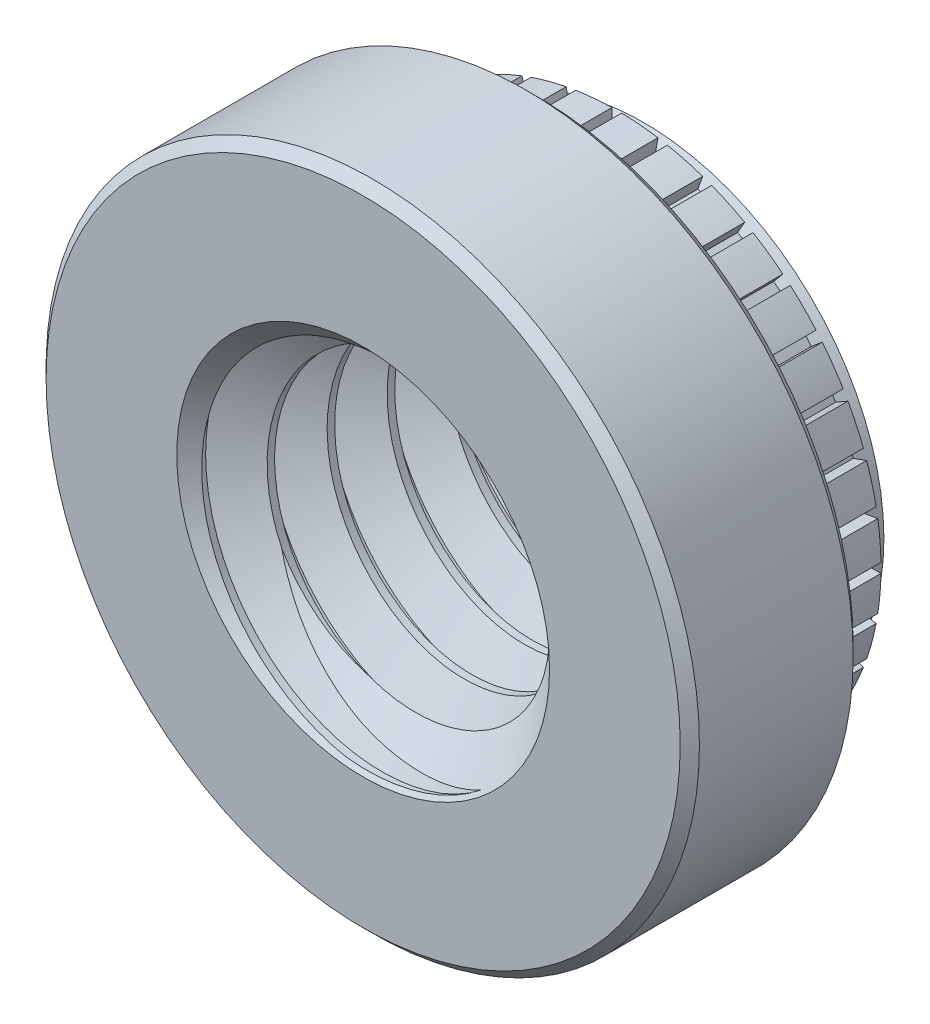
SolidWorks part; units mm, degrees
ref_plane "Front Plane" through (0, 0, 0) normal (0, 0, 1) x (1, 0, 0)
ref_plane "Top Plane" through (0, 0, 0) normal (0, 1, 0) x (1, 0, 0)
ref_plane "Right Plane" through (0, 0, 0) normal (1, 0, 0) x (0, 0, -1)
sketch "Sketch1" plane through (0, 0, 0) normal (0, 0, 1) x (1, 0, 0)
  circle A0 centre (0, 0) radius 4.318
  dimension "A" = 8.636
extrude "Extrude1" add sketch "Sketch1" against normal blind 2.286
sketch "Sketch15" plane through (0, 0, -2.286) normal (0, 0, -1) x (-1, 0, 0)
  circle A0 centre (0, 0) radius 3.175
  dimension "hole dia" = 6.35
sketch "Sketch2" plane through (0, 0, -2.286) normal (0, 0, -1) x (-1, 0, 0)
  circle A0 centre (0, 0) radius 3.4925
  dimension "D1" = 6.985
extrude "Extrude2" add sketch "Sketch2" along normal blind 1.4224
sketch "Sketch3" plane through (0, 0, -3.7084) normal (0, 0, -1) x (-1, 0, 0)
  line L0 (0, 3.302) -> (0, 4.318)
  circle A1 centre (0, 0) radius 4.318 construction
  circle A2 centre (0, 0) radius 3.302
  circle A3 centre (0, 0) radius 3.302 construction
  dimension "D1" = 0.1905
extrude "Cut-Extrude-Thin1" cut sketch "Sketch3" against normal up to surface (1.4224 mm away) thin up to face at (4.318, 0, -2.286) thin type mid plane wall 0.127
pattern_circular "CirPattern1" count 36 over 360 about axis through (0, 0, 0) along (0, 0, 1) of "Cut-Extrude-Thin1"
sketch "Sketch5" plane through (0, 0, -3.7084) normal (0, 0, -1) x (-1, 0, 0)
  circle A0 centre (0, 0) radius 4.318 construction
  circle A3 centre (0, 0) radius 3.175
  dimension "C" = 6.35
extrude "Cut-Extrude1" cut sketch "Sketch5" against normal blind 0.3556 draft 20 flip side to cut draft outward yes
chamfer "Chamfer2" distance 0.127 angle 45 2 edges at (4.318, 0, 0) (4.318, 0, -2.286)
sketch "Sketch7" plane through (0, 0, 0) normal (0, 0, 1) x (1, 0, 0)
  circle A0 centre (0, 0) radius 2.413
  dimension "Thread Od" = 4.826
extrude "Cut-Extrude3" cut sketch "Sketch7" against normal through all
sketch "Sketch8" plane through (0, 0, -3.7084) normal (0, 0, -1) x (-1, 0, 0)
  circle A0 centre (0, 0) radius 2.413 construction
  circle A1 centre (0, 0) radius 2.413
curve "Helix/Spiral1" pitch 0.7937 height 6.8834 turns 8.672 parameters "pitch"=0.7937
sketch "Sketch9" plane through (0, 0, 0) normal (1, 0, 0) x (0, 0, -1)
  line L0 (4.4029, 2.413) -> (4.1053, 1.8974)
  line L1 (4.1053, 1.8974) -> (4.0061, 1.8974)
  line L2 (4.0061, 1.8974) -> (3.7084, 2.413)
  line L3 (4.4029, 2.413) -> (3.7084, 2.413)
  line L4 (4.0557, 2.413) -> (4.0557, 1.8974) construction
  line L5 (4.2541, 2.1552) -> (3.8572, 2.1552) construction
  line L6 (3.7084, -2.413) -> (3.7084, 2.413) construction
  dimension "D1" = 60
  dimension "D2" = 0.0992
  dimension "D3" = 0.3969
sweep "Sweep1" add profiles "Sketch9" path "Helix/Spiral1"
sketch "Sketch10" plane through (0, 0, 0) normal (0, 0, 1) x (1, 0, 0)
  circle A0 centre (0, 0) radius 4.318 construction
  circle A1 centre (0, 0) radius 4.318
extrude "Cut-Extrude4" cut sketch "Sketch10" along normal through all
sketch "Sketch11" plane through (0, 0, -3.7084) normal (0, 0, -1) x (-1, 0, 0)
  circle A1 centre (0, 0) radius 3.175 construction
  circle A2 centre (0, 0) radius 3.175
extrude "Cut-Extrude5" cut sketch "Sketch11" along normal through all
sketch "Sketch13" plane through (0, 0, 0) normal (0, 0, 1) x (1, 0, 0)
  circle A2 centre (0, 0) radius 2.4638
  circle A3 centre (0, 0) radius 2.4638
  dimension "D1" = 0.0508
extrude "Cut-Extrude6" cut sketch "Sketch13" against normal through all draft 45
sketch "Sketch14" plane through (0, 0, -3.7084) normal (0, 0, -1) x (-1, 0, 0)
  circle A2 centre (0, 0) radius 2.4638
  circle A3 centre (0, 0) radius 2.4638
  dimension "D1" = 0.0508
extrude "Cut-Extrude7" cut sketch "Sketch14" against normal through all draft 45
equation "\"D3@Helix/Spiral1\" = \"B@Extrude1\"+\"panel min.@Extrude2\"+.125"
equation "\"D2@Sketch9\" = \"pitch@Helix/Spiral1\"*.125"
equation "\"D3@Sketch9\" = \"pitch@Helix/Spiral1\"*.50"
equation "\"D1@Sketch2\" = \"hole dia@Sketch15\"+.025"
equation "\"D1@Cut-Extrude1\" = \"panel min.@Extrude2\"*.25"
